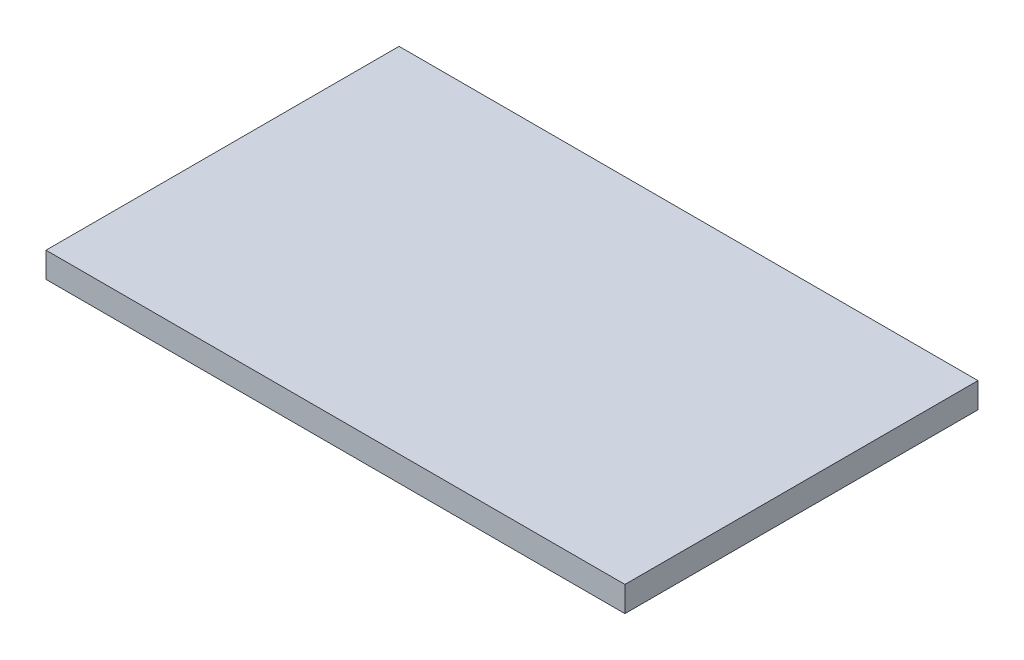
SolidWorks part; units mm, degrees
ref_plane "Front Plane" through (0, 0, 0) normal (0, 0, 1) x (1, 0, 0)
ref_plane "Top Plane" through (0, 0, 0) normal (0, 1, 0) x (1, 0, 0)
ref_plane "Right Plane" through (0, 0, 0) normal (1, 0, 0) x (0, 0, -1)
ref_plane "Плоскость1" through (0, -4, 0) normal (0, 1, 0) x (1, 0, 0)
ref_plane "Plan2" through (0, 0, 0) normal (0, 1, 0) x (1, 0, 0)
sketch "Эскиз1" plane through (0, 0, 0) normal (0, 1, 0) x (1, 0, 0)
  line L0 (-43.2934, -27.2) -> (-40.6, -27.2)
  line L4 (-43.2934, -27.2) -> (-43.2934, -23.2)
  line L5 (40.6, -27.2) -> (45.9066, -27.2)
  line L6 (40.6, 27.2) -> (40.6, 27.1943) construction
  line L7 (40.6, 27.2) -> (-40.6, 27.2)
  line L11 (-40.6, 27.2) -> (-40.6, 27.1844) construction
  line L13 (-40.6, -27.2) -> (40.6, -27.2)
  line L20 (-43.2934, 23.2) -> (-43.2934, -23.2)
  line L24 (45.9066, -23.2) -> (45.9066, 23.2)
  line L28 (-43.2934, 23.2) -> (-43.2934, 27.2)
  line L42 (45.9066, -27.2) -> (45.9066, -23.2)
  line L43 (40.6, 27.1943) -> (45.9066, 27.1943)
  line L45 (45.9066, 27.1943) -> (45.9066, 23.2)
  line L47 (-43.2934, 27.2) -> (-40.6, 27.2)
  point P37 (1.3066, 0)
  point P42 (0, 0)
  dimension "D2" = 40.6
  dimension "D9" = 23.2
  dimension "D1" = 1.3066
  dimension "D3" = 45.9066
  dimension "D4" = 40.6
  dimension "D5" = 43.2934
  dimension "D6" = 23.2
  dimension "D7" = 27.1943
  dimension "D8" = 27.2
extrude "Бобышка-Вытянуть1" add sketch "Эскиз1" along normal blind 3.9 rebuild error yes
sketch "Эскиз2" plane through (0, -4, 0) normal (0, 1, 0) x (1, 0, 0)
  line L0 (0, 0) -> (0, 45) construction
  line L1 (-45, 45) -> (45, 45) construction
  line L2 (-44.3008, 45) -> (-45, 45) construction
  line L3 (-45, 45) -> (-45, -45) construction
  line L4 (-45, -45) -> (45, -45) construction
  line L5 (45, -45) -> (45, 45) construction
  line L6 (-45, 0) -> (0, 0) construction
  dimension "D1" = 90
  dimension "D2" = 45
  dimension "D3" = 90
  dimension "D4" = 45
sketch "Эскиз3" plane through (0, 0, 0) normal (0, 0, 1) x (1, 0, 0)
  line L0 (-45, -4) -> (45, -4) construction
  line L1 (-45, -4) -> (45, -4) construction
  line L2 (-44.8219, -4) -> (-44.8219, -6.4999) construction
  line L5 (-47.8153, -6.4999) -> (-45.8419, -6.4999)
  line L7 (-43.8019, -6.4999) -> (-41.8285, -6.4999)
  arc A0 (-43.8019, -6.4999) -> (-45.8419, -6.4999) centre (-44.8219, -4) ccw
  arc A1 (-41.8285, -6.4999) -> (-47.8153, -6.4999) centre (-44.8219, -4) ccw
  point P7 (-45.8419, -6.4999)
  point P9 (-43.8019, -6.4999)
  dimension "D1" = 5.4
  dimension "D2" = 7.8
  dimension "D4" = 45
  dimension "D3" = 2.04
  dimension "D5" = 2.9934
  dimension "D6" = 2.4999
extrude "Бобышка-Вытянуть3" add sketch "Эскиз3" along normal mid plane 40
sketch "Esquisse1" plane through (0, 0, 0) normal (0, 1, 0) x (1, 0, 0)
  line L0 (1.31, 27.2) -> (1.31, -27.2) construction
  line L1 (-43.29, 27.2) -> (45.91, 27.2)
  line L2 (-43.29, 27.2) -> (-43.29, -27.2)
  line L3 (-43.29, -27.2) -> (45.91, -27.2)
  line L4 (45.91, 27.2) -> (45.91, -27.2)
  line L5 (45.91, 0) -> (-43.29, 0) construction
  point P8 (1.31, 0)
  dimension "D1" = 1.31
  dimension "D2" = 45.91
  dimension "D3" = 27.2
  dimension "D4" = 27.2
extrude "Boss.-Extru.1" add sketch "Esquisse1" along normal blind 3.9
sketch "Эскиз5" [suppressed] plane through (0, 0, 0) normal (0, 0, 1) x (1, 0, 0)
  line L1 (-40.6, 0) -> (40.6, 0) construction
  line L2 (-37.7102, 0) -> (-38.9828, 0)
  arc A0 (-37.7102, 0) -> (-46.8472, -0.6672) centre (-41.8285, -6.4999) ccw
  arc A1 (-38.9828, 0) -> (-41.0081, -4.8154) centre (-27.3047, -7.7451) ccw
  arc A2 (-41.8285, -6.4999) -> (-47.8153, -6.4999) centre (-44.8219, -4) ccw construction
  arc A3 (-41.0081, -4.8154) -> (-46.8472, -0.6672) centre (-44.8219, -4) ccw
  point P5 (-46.8472, -0.6672)
  point P14 (-38.9828, 0)
  dimension "D1" = 7.6947
  dimension "D2" = 14.0131
  dimension "D3" = 27.3047
extrude "Бобышка-Вытянуть5" [suppressed] add sketch "Эскиз5" along normal mid plane 40
fillet "Скругление1" radius 0.25 2 edges at (-43.8019, -6.4999, 0) (-45.8419, -6.4999, 0)
sketch "Эскиз7" plane through (0, 0, 20) normal (0, 0, 1) x (1, 0, 0)
  line L0 (-45, -4) -> (45, -4) construction
  line L1 (49.5, -4) -> (-49.5, -4) construction
  circle A0 centre (-45, -4) radius 5.5
  dimension "D1" = 11
sketch "Эскиз8" [suppressed] plane through (0, 0, 0) normal (0, 1, 0) x (1, 0, 0)
  line L1 (-39.4537, 20) -> (-31.4537, 20)
  line L3 (-39.4537, -20) -> (-31.4537, -20)
  line L4 (-31.4537, 20) -> (-31.4537, -20)
  line L6 (-37.7102, 20) -> (-46.8472, 20) construction
  line L7 (-39.4537, 20) -> (-45, 20)
  line L8 (-45, 45) -> (-45, -45) construction
  line L9 (-45, 20) -> (-45, -20)
  line L10 (-50.5, -20) -> (-39.5, -20) construction
  line L11 (-45, -20) -> (-39.4537, -20)
  point P6 (0, 0)
  dimension "D1" = 40
  dimension "D2" = 8
extrude "Бобышка-Вытянуть6" [suppressed] add sketch "Эскиз8" along normal blind 2
sketch "Эскиз9" [suppressed] plane through (0, 2, 0) normal (0, 1, 0) x (1, 0, 0)
  line L1 (-37, -15) -> (-37, 0) construction
  line L4 (-37, 15) -> (-37, 0) construction
  line L5 (-45, 0) -> (0, 0) construction
  circle A0 centre (-37, 15) radius 1.5
  circle A1 centre (-37, -15) radius 1.5
  dimension "D1" = 3
  dimension "D2" = 37
  dimension "D3" = 37
  dimension "D4" = 30
  dimension "D5" = 15
extrude "Вырез-Вытянуть1" [suppressed] cut sketch "Эскиз9" against normal through all
fillet "Скругление2" [suppressed] radius 10
